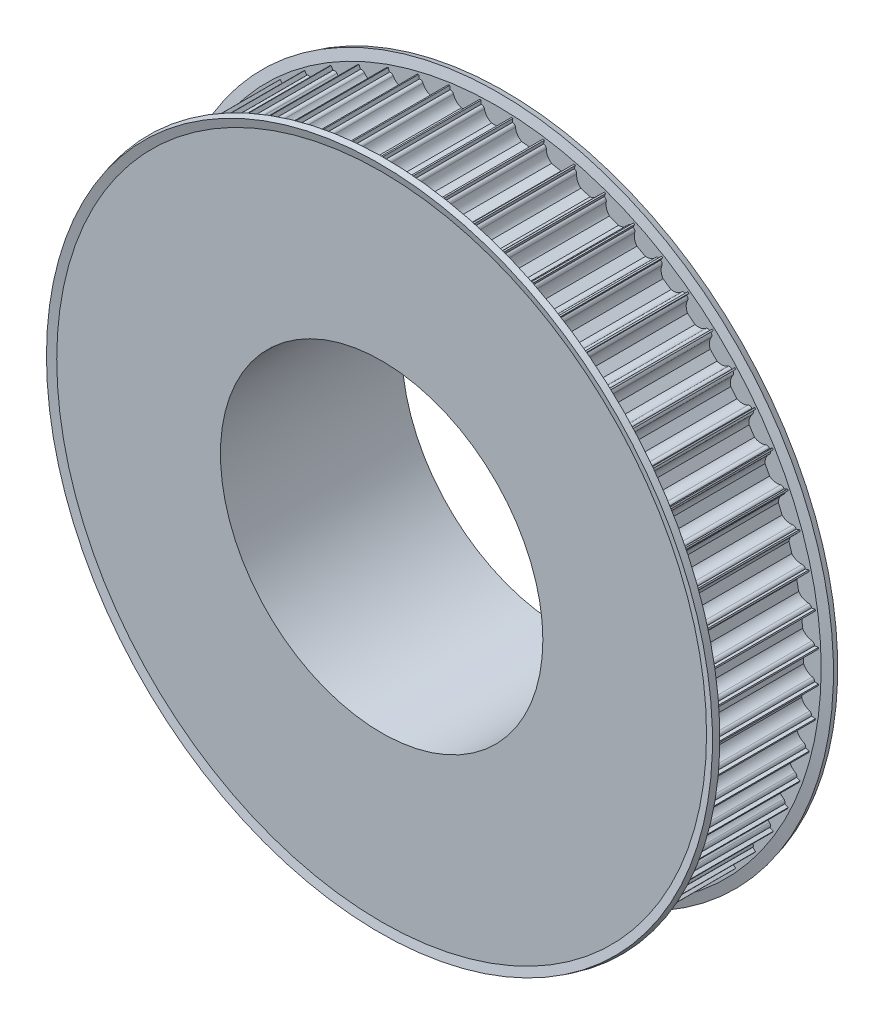
SolidWorks part; units mm, degrees
ref_plane "Front Plane" through (0, 0, 0) normal (0, 0, 1) x (1, 0, 0)
ref_plane "Top Plane" through (0, 0, 0) normal (0, 1, 0) x (1, 0, 0)
ref_plane "Right Plane" through (0, 0, 0) normal (1, 0, 0) x (0, 0, -1)
sketch "Sketch1" plane through (0, 0, 0) normal (1, 0, 0) x (0, 0, -1)
  line L0 (0, 0) -> (17.7994, 0) construction
  line L1 (0, 40) -> (45, 40)
  line L2 (45, 40) -> (45, 55.5)
  line L3 (45, 55.5) -> (30, 55.5)
  line L4 (30, 55.5) -> (30, 80)
  line L5 (30, 80) -> (0, 80)
  line L6 (0, 80) -> (0, 40)
  point P9 (0, 0)
  dimension "D1" = 40
  dimension "D2" = 80
  dimension "D3" = 15.5
  dimension "D4" = 30
  dimension "D5" = 45
revolve "Revolve1" add sketch "Sketch1" angle 360 about L0
sketch "Sketch2" plane through (0, 0, 0) normal (0, 0, 1) x (1, 0, 0)
  line L0 (-3.6742, 79) -> (-3.75, 79)
  line L1 (-3.75, 79) -> (-3.75, 81)
  line L2 (-3.75, 81) -> (3.75, 81)
  line L3 (3.75, 81) -> (3.75, 79)
  line L4 (3.75, 79) -> (3.6742, 79)
  line L5 (1.199, 76.25) -> (-1.199, 76.25)
  arc A0 (2.9394, 78.4) -> (1.199, 76.25) centre (0, 79) cw
  arc A1 (2.9394, 78.4) -> (3.6742, 79) centre (3.6742, 78.25) cw
  arc A2 (-2.9394, 78.4) -> (-3.6742, 79) centre (-3.6742, 78.25) ccw
  arc A3 (-1.199, 76.25) -> (-2.9394, 78.4) centre (0, 79) cw
  point P6 (0, 81)
  point P11 (3, 79)
  point P14 (-3, 79)
  dimension "D1" = 3
  dimension "D5" = 0.75
  dimension "D2" = 79
  dimension "D3" = 7.5
  dimension "D4" = 2
  dimension "D6" = 2.75
extrude "Cut-Extrude1" cut sketch "Sketch2" against normal up to next
pattern_circular "CirPattern1" count 64 over 360 about axis through (0, 0, 0) along (0, 0, 1) of "Cut-Extrude1"
sketch "Sketch3" plane through (0, 0, 0) normal (1, 0, 0) x (0, 0, -1)
  line L0 (15, -40.9775) -> (15, -16.0516) construction
  line L1 (30, -40.9775) -> (0, -40.9775) construction
  line L2 (30, -16.0516) -> (0, -16.0516) construction
  line L3 (30, 55.5) -> (30, 80.61)
  line L4 (30, 80.61) -> (30.5391, 82.6218)
  line L5 (30.5391, 82.6218) -> (29.0902, 83.01)
  line L6 (29.0902, 83.01) -> (28.4471, 80.61)
  line L7 (28.4471, 80.61) -> (28.4471, 55.5)
  line L8 (28.4471, 55.5) -> (30, 55.5)
  line L9 (45, 55.5) -> (30, 55.5) construction
  line L10 (1.5529, 80.61) -> (1.5529, 55.5)
  line L11 (0.9098, 83.01) -> (1.5529, 80.61)
  line L12 (-0.5391, 82.6218) -> (0.9098, 83.01)
  line L13 (0, 80.61) -> (-0.5391, 82.6218)
  line L14 (0, 55.5) -> (0, 80.61)
  line L15 (1.5529, 55.5) -> (0, 55.5)
  line L16 (0, 0) -> (-18.1407, 0) construction
  dimension "D1" = 15
  dimension "D2" = 25.11
  dimension "D3" = 1.5
  dimension "D4" = 2.4
revolve "Revolve4" add sketch "Sketch3" angle 360 about L16
